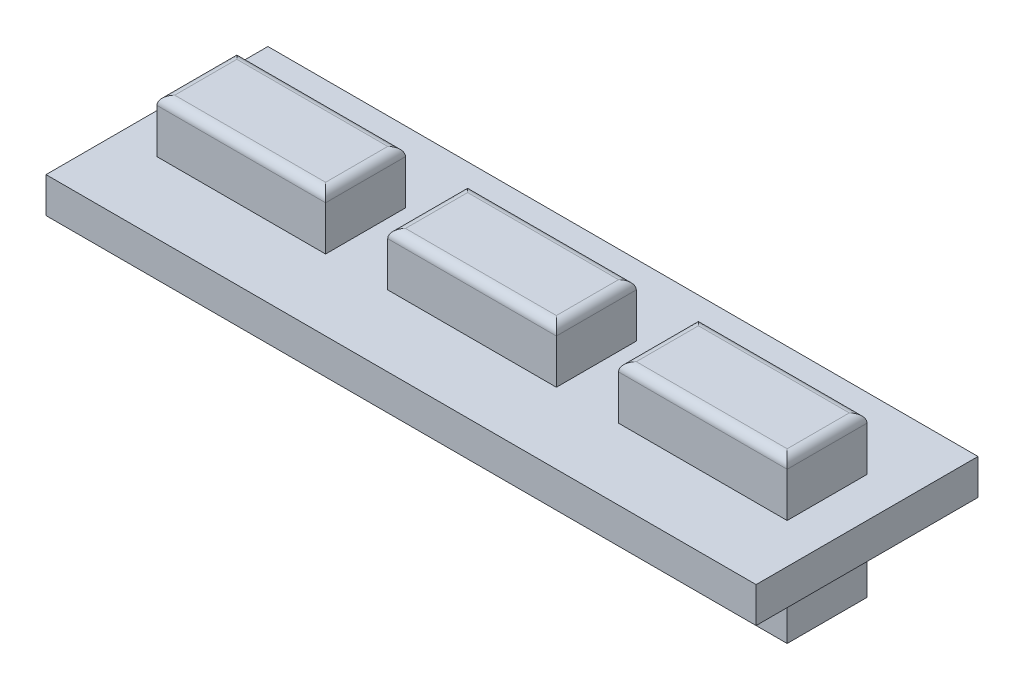
SolidWorks part; units mm, degrees
ref_plane "Front Plane" through (0, 0, 0) normal (0, 0, 1) x (1, 0, 0)
ref_plane "Top Plane" through (0, 0, 0) normal (0, 1, 0) x (1, 0, 0)
ref_plane "Right Plane" through (0, 0, 0) normal (1, 0, 0) x (0, 0, -1)
ref_plane "Plane1" through (0, 3.048, 0) normal (0, 1, 0) x (1, 0, 0)
sketch "Sketch1" plane through (0, 3.048, 0) normal (0, 1, 0) x (1, 0, 0)
  line L1 (-10.1507, 28.7595) -> (10.1693, 28.7595)
  line L2 (-10.1507, 28.7595) -> (-10.1507, 22.4095)
  line L3 (-10.1507, 22.4095) -> (10.1693, 22.4095)
  line L4 (10.1693, 28.7595) -> (10.1693, 22.4095)
  line L5 (-9.0077, 26.7275) -> (-4.1817, 26.7275)
  line L6 (-9.0077, 26.7275) -> (-9.0077, 24.4415)
  line L7 (-9.0077, 24.4415) -> (-4.1817, 24.4415)
  line L8 (-4.1817, 26.7275) -> (-4.1817, 24.4415)
  line L9 (-2.4037, 26.7275) -> (2.4223, 26.7275)
  line L10 (-2.4037, 26.7275) -> (-2.4037, 24.4415)
  line L11 (-2.4037, 24.4415) -> (2.4223, 24.4415)
  line L12 (2.4223, 26.7275) -> (2.4223, 24.4415)
  line L13 (4.2003, 26.7275) -> (9.0263, 26.7275)
  line L14 (4.2003, 26.7275) -> (4.2003, 24.4415)
  line L15 (4.2003, 24.4415) -> (9.0263, 24.4415)
  line L16 (9.0263, 26.7275) -> (9.0263, 24.4415)
  point P16 (-4.1817, 25.5845)
  point P17 (-10.1507, 25.5845)
  point P18 (0.0093, 28.7595)
  point P19 (0.0093, 26.7275)
  dimension "D1" = 2.286
  dimension "D2" = 4.826
  dimension "D3" = 4.826
  dimension "D4" = 4.826
  dimension "D5" = 1.778
  dimension "D6" = 1.778
  dimension "D7" = 6.35
  dimension "D8" = 20.32
extrude "Boss-Extrude1" add sketch "Sketch1" along normal blind 2.032 and the other way blind 2.54 contours L8 L5 L6 L7 | L12 L9 L10 L11 | L16 L13 L14 L15 | L12 L11 L10 L9 | L14 L15 L16 L13 region at (-6.5947, 3.048, -25.5845) region at (0.0093, 3.048, -25.5845) region at (6.6133, 3.048, -25.5845)
extrude "Boss-Extrude2" add sketch "Sketch1<3>" along normal blind 0.508 and the other way blind 0.508 contours L3 L4 L1 L2
sketch "Sketch1<3>" plane through (0, 3.048, 0) normal (0, 1, 0) x (1, 0, 0) same geometry as "Sketch1"
fillet "Fillet1" radius 0.254 12 edges at (0.0093, 5.08, -24.4415) (-2.4037, 5.08, -25.5845) (0.0093, 5.08, -26.7275) (2.4223, 5.08, -25.5845) (-6.5947, 5.08, -24.4415) (-9.0077, 5.08, -25.5845) (-6.5947, 5.08, -26.7275) (-4.1817, 5.08, -25.5845) (6.6133, 5.08, -24.4415) (4.2003, 5.08, -25.5845) (6.6133, 5.08, -26.7275) (9.0263, 5.08, -25.5845)
